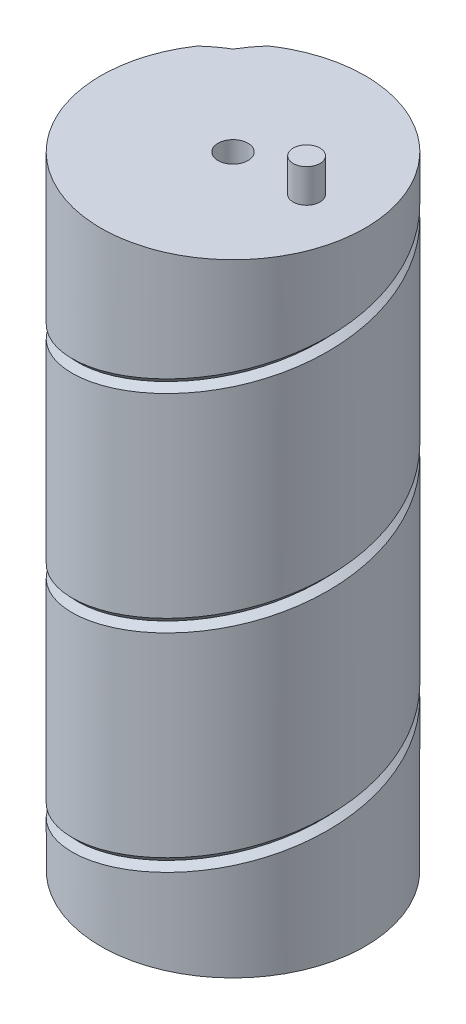
SolidWorks part; units mm, degrees
ref_plane "Front Plane" through (0, 0, 0) normal (0, 0, 1) x (1, 0, 0)
ref_plane "Top Plane" through (0, 0, 0) normal (0, 1, 0) x (1, 0, 0)
ref_plane "Right Plane" through (0, 0, 0) normal (1, 0, 0) x (0, 0, -1)
sketch "Sketch1" plane through (0, 0, 0) normal (0, 1, 0) x (1, 0, 0)
  line L0 (-19.75, 0) -> (19.75, 0) construction
  circle A0 centre (0, 0) radius 19.75
  dimension "D1" = 39.5
curve "Helix - Antenna Guide" pitch 31 height 93 radius 19.75 centre (0, 0, 0) axis (0, 1, 0) start towards (0, 0, 1)
extrude "Extrude - Main Body" add sketch "Sketch1<2>" along normal blind 93
sketch "Sketch1<2>" plane through (0, 0, 0) normal (0, 1, 0) x (1, 0, 0) same geometry as "Sketch1"
ref_point "Point2"
ref_point "Point1"
ref_plane "Plane1" through (-13.9654, 0, -13.9654) normal (-0.686, 0.2424, 0.686) x (-0.7276, -0.2285, -0.6468)
sketch "Sketch15" plane through (-13.9654, 0, -13.9654) normal (-0.686, 0.2424, 0.686) x (-0.7276, -0.2285, -0.6468)
  line L4 (0, 0) -> (0.2165, 0.8934)
  line L5 (0.2165, 0.8934) -> (-0.8934, 0.2165)
  line L8 (0, 0) -> (-0.2165, -0.8934)
  line L9 (-0.2165, -0.8934) -> (-0.8934, 0.2165)
  point P7 (-0.5549, -0.3384)
  dimension "D1" = 0.65
  dimension "D2" = 90
sweep "Cut - Antenna Wire Guide" cut profiles "Sketch15" path "Helix - Antenna Guide" align with end faces yes
sketch "Sketch23" plane through (0, 0, 0) normal (0, -1, 0) x (1, 0, 0)
  line L0 (-13.3154, -13.3154) -> (-8.3849, -14.1466)
  line L1 (-9.335, -17.4046) -> (-10.0329, -12.4535)
  arc A0 (-11.0473, -16.3713) -> (-16.3713, -11.0473) centre (0, 0) ccw construction
  arc A1 (-10.0329, -12.4535) -> (-8.3849, -14.1466) centre (-8.0525, -12.1744) cw
  arc A2 (-9.335, -17.4046) -> (-13.3154, -13.3154) centre (-14.1184, -18.0788) cw
  dimension "D2" = 2
  dimension "D1" = 2
  dimension "D3" = 5
  dimension "D4" = 5
ref_plane "Plane - Anchor Loop Exit" through (-9.335, 0, -17.4046) normal (-0.1396, 0, 0.9902) x (0.9902, 0, 0.1396)
ref_plane "Plane - Anchor Loop Peg" through (-10.0329, 0, -12.4535) normal (-0.1396, 0, 0.9902) x (0.9902, 0, 0.1396)
sketch "Sketch28" plane through (0, 93, 0) normal (0, 1, 0) x (1, 0, 0)
  circle A0 centre (11, 0) radius 2
  point P0 (0, 0)
  dimension "D1" = 4
  dimension "D2" = 11
extrude "Extruded Peg" add sketch "Sketch28" along normal blind 5
hole_wizard "Hole for Threaded Rod" positions "Sketch29" profile "Sketch30" hole size "#8" standard "ANSI Inch" end condition through all
sketch "Sketch29" plane through (0, 93, 0) normal (0, 1, 0) x (1, 0, 0)
  point P0 (0, 0)
sketch "Sketch30" plane through (0, 93, 0) normal (1, 0, 0) x (0, 0, 1)
  line L0 (0, 0) -> (0, 94.4693)
  line L1 (0, 94.4693) -> (2.2479, 94.4693)
  line L2 (2.2479, 94.4693) -> (2.2479, 0)
  line L5 (2.2479, 0) -> (0, 0)
  line L11 (0, -6.35) -> (0, 107.95) construction
  dimension "Thru Hole Dia." = 4.4958
  dimension "Thru Hole Depth" = 94.4693
sketch "Sketch31" plane through (0, 0, 0) normal (0, -1, 0) x (1, 0, 0)
  circle A0 centre (11, 0) radius 2.25
  dimension "D1" = 4.5
  dimension "D2" = 11
extrude "Cut Peg" cut sketch "Sketch31" against normal blind 5.5
equation "\"pegD\"=10"
equation "\"pegHoleD\"=0.5"
equation "\"pegHoleOffset\"=0.5"
